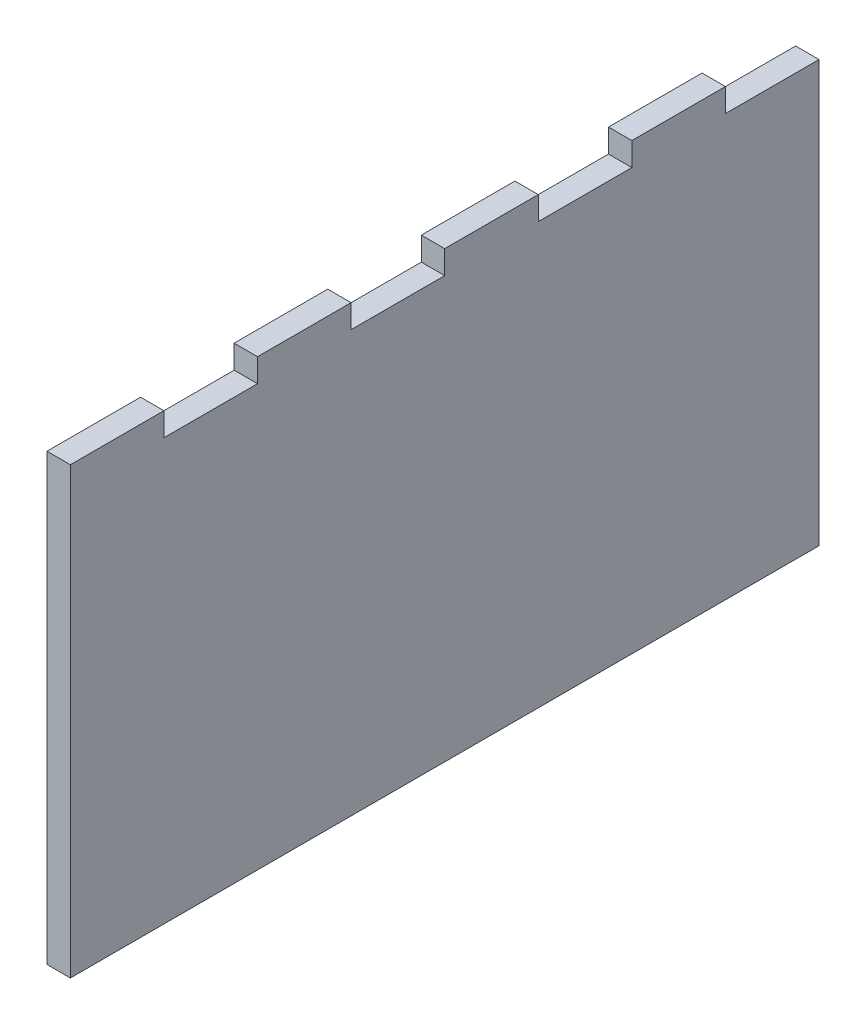
SolidWorks part; units mm, degrees
ref_plane "Front Plane" through (0, 0, 0) normal (0, 0, 1) x (1, 0, 0)
ref_plane "Top Plane" through (0, 0, 0) normal (0, 1, 0) x (1, 0, 0)
ref_plane "Right Plane" through (0, 0, 0) normal (1, 0, 0) x (0, 0, -1)
sketch "Sketch1" plane through (0, 0, 0) normal (1, 0, 0) x (0, 0, -1)
  line L0 (0, 0) -> (0, 60.325)
  line L1 (0, 60.325) -> (12.7, 60.325)
  line L2 (12.7, 57.15) -> (25.4, 57.15)
  line L3 (25.4, 57.15) -> (25.4, 60.325)
  line L4 (25.4, 60.325) -> (38.1, 60.325)
  line L5 (38.1, 60.325) -> (38.1, 57.15)
  line L6 (38.1, 57.15) -> (50.8, 57.15)
  line L7 (50.8, 57.15) -> (50.8, 60.325)
  line L8 (50.8, 60.325) -> (63.5, 60.325)
  line L9 (63.5, 60.325) -> (63.5, 57.15)
  line L10 (63.5, 57.15) -> (76.2, 57.15)
  line L11 (76.2, 57.15) -> (76.2, 60.325)
  line L12 (76.2, 60.325) -> (88.9, 60.325)
  line L13 (88.9, 60.325) -> (88.9, 57.15)
  line L14 (88.9, 57.15) -> (101.6, 57.15)
  line L15 (101.6, 57.15) -> (101.6, 0)
  line L16 (101.6, 0) -> (0, 0)
  line L17 (12.7, 60.325) -> (12.7, 57.15)
  dimension "D1" = 101.6
  dimension "D2" = 3.175
  dimension "D10" = 57.15
extrude "Boss-Extrude1" add sketch "Sketch1" along normal blind 3.175
